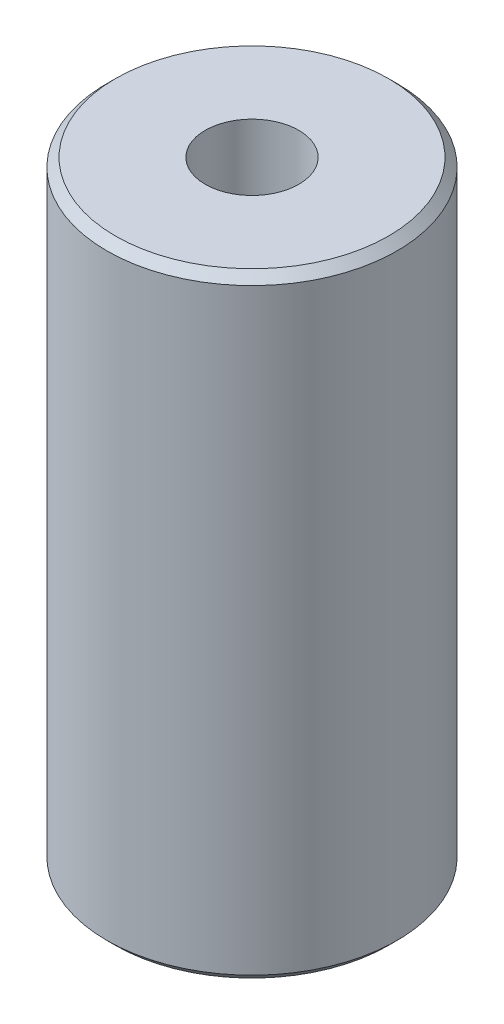
SolidWorks part; units mm, degrees
ref_plane "Front Plane" through (0, 0, 0) normal (0, 0, 1) x (1, 0, 0)
ref_plane "Top Plane" through (0, 0, 0) normal (0, 1, 0) x (1, 0, 0)
ref_plane "Right Plane" through (0, 0, 0) normal (1, 0, 0) x (0, 0, -1)
sketch "Sketch1" plane through (0, 0, 0) normal (0, 1, 0) x (1, 0, 0)
  circle A0 centre (0, 0) radius 22.5
  dimension "SHAFT_OD" = 45
extrude "Boss-Extrude1" add sketch "Sketch1" along normal blind 95.3009
sketch "Sketch2" plane through (0, 0, 0) normal (0, 1, 0) x (1, 0, 0)
  circle A0 centre (0, 0) radius 7.2594
  dimension "BORE_D" = 14.5188
extrude "Cut-Extrude1" cut sketch "Sketch2" along normal through all
chamfer "Chamfer1" distance 1.3294 angle 45 2 edges at (0, 95.3009, 22.5) (0, 0, 22.5)
